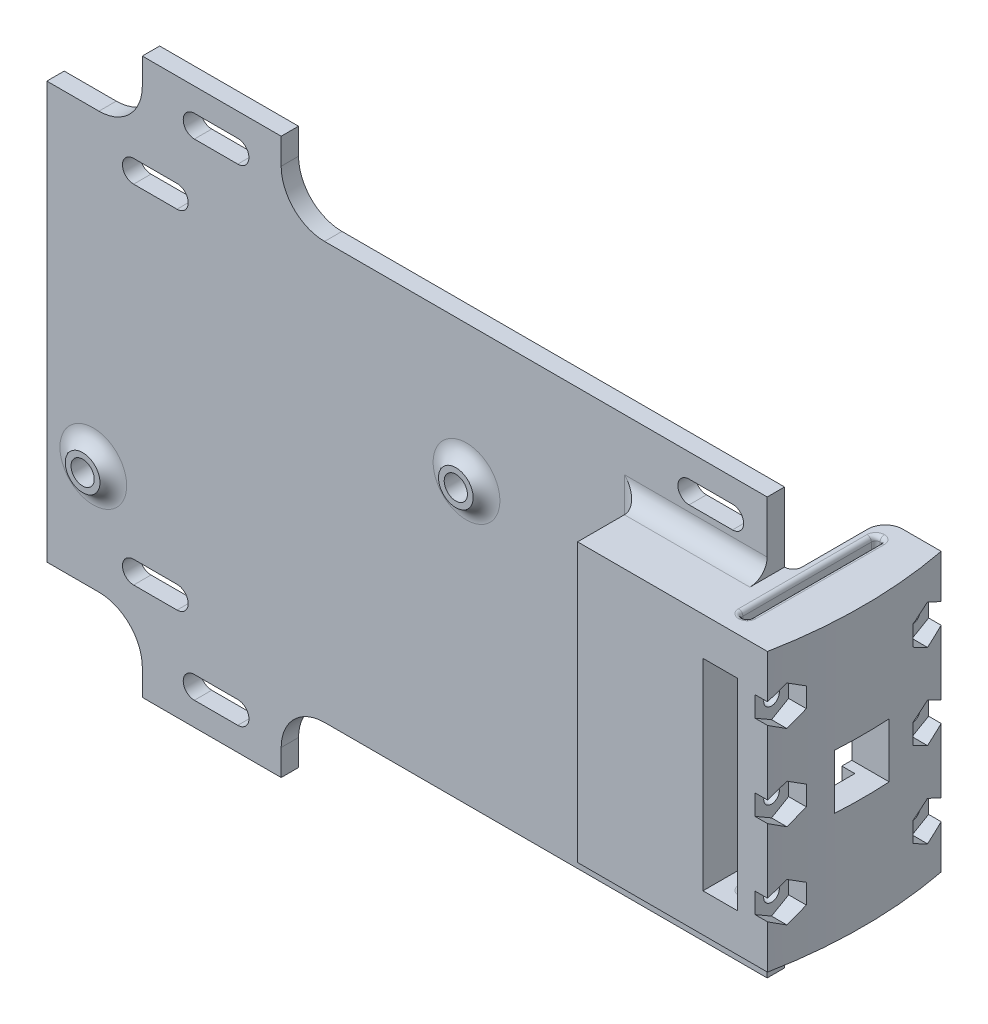
SolidWorks part; units mm, degrees
ref_plane "Front Plane" through (0, 0, 0) normal (0, 0, 1) x (1, 0, 0)
ref_plane "Top Plane" through (0, 0, 0) normal (0, 1, 0) x (1, 0, 0)
ref_plane "Right Plane" through (0, 0, 0) normal (1, 0, 0) x (0, 0, -1)
sketch "Sketch1" plane through (0, 0, 0) normal (0, 0, 1) x (1, 0, 0)
  line L1 (52.705, 30.48) -> (-52.705, 30.48)
  line L2 (52.705, 30.48) -> (52.705, -30.48)
  line L3 (52.705, -30.48) -> (-52.705, -30.48)
  line L4 (-52.705, 30.48) -> (-52.705, -30.48)
  line L5 (52.705, 30.48) -> (-52.705, -30.48) construction
  line L6 (52.705, -30.48) -> (-52.705, 30.48) construction
  point P0 (0, 0)
  dimension "D1" = 105.41
  dimension "D2" = 60.96
extrude "Boss-Extrude1" add sketch "Sketch1" along normal blind 2.54
sketch "Sketch20" plane through (0, 30.48, 0) normal (0, 1, 0) x (1, 0, 0)
  line L0 (52.705, -2.54) -> (-52.705, -2.54) construction
  line L1 (-38.735, -2.54) -> (-18.415, -2.54)
  line L2 (-38.735, -2.54) -> (-38.735, 0)
  line L3 (-38.735, 0) -> (-18.415, 0)
  line L4 (-18.415, -2.54) -> (-18.415, 0)
  line L5 (52.705, 0) -> (-52.705, 0) construction
  line L6 (-52.705, -2.54) -> (-52.705, 0) construction
  dimension "D1" = 13.97
  dimension "D2" = 20.32
extrude "Boss-Extrude5" add sketch "Sketch20" along normal blind 10.16
sketch "Sketch21" plane through (0, -30.48, 0) normal (0, -1, 0) x (-1, 0, 0)
  line L0 (52.705, -2.54) -> (-52.705, -2.54) construction
  line L1 (18.415, -2.54) -> (38.735, -2.54)
  line L2 (18.415, -2.54) -> (18.415, 0)
  line L3 (18.415, 0) -> (38.735, 0)
  line L4 (38.735, -2.54) -> (38.735, 0)
  line L5 (52.705, 0) -> (-52.705, 0) construction
  line L6 (52.705, -2.54) -> (52.705, 0) construction
  dimension "D1" = 13.97
  dimension "D2" = 20.32
extrude "Boss-Extrude6" add sketch "Sketch21" along normal blind 10.16
sketch "Sketch3" plane through (0, 0, 2.54) normal (0, 0, 1) x (1, 0, 0)
  line L0 (0, 0) -> (119.7861, 0) construction
  line L1 (34.356, 20.32) -> (52.705, 20.32)
  line L2 (34.356, 20.32) -> (34.356, -20.32)
  line L3 (34.356, -20.32) -> (52.705, -20.32)
  line L4 (52.705, 20.32) -> (52.705, -20.32)
  line L5 (52.705, -30.48) -> (52.705, 30.48) construction
  dimension "D1" = 40.64
  dimension "D3" = 18.349
extrude "Boss-Extrude2" add sketch "Sketch3" along normal blind 9.398
sketch "Sketch4" plane through (34.356, 0, 0) normal (-1, 0, 0) x (0, 0, 1)
  line L0 (2.54, 20.32) -> (2.54, -20.32) construction
  line L1 (11.0109, 11.43) -> (8.89, 11.43)
  line L2 (11.0109, 11.43) -> (11.0109, -12.5705)
  line L3 (11.0109, -12.5705) -> (8.89, -12.5705)
  line L4 (8.89, 11.43) -> (8.89, -12.5705)
  line L5 (11.938, 20.32) -> (2.54, 20.32) construction
  dimension "D1" = 2.1209
  dimension "D2" = 24.0005
  dimension "D3" = 6.35
  dimension "D4" = 8.89
extrude "SD card Slot" cut sketch "Sketch4" against normal blind 16.51
sketch "Sketch6" plane through (0, 0, 2.54) normal (0, 0, 1) x (1, 0, 0)
  line L0 (50.866, 11.43) -> (50.866, -12.5705) construction
  line L1 (50.866, 11.43) -> (34.356, 11.43) construction
  circle A0 centre (-45.908, -14.954) radius 2.54
  circle A1 centre (8.702, 10.446) radius 2.54
  dimension "D1" = 5.08
  dimension "D2" = 5.08
  dimension "D3" = 54.61
  dimension "D4" = 25.4
  dimension "D5" = 42.164
  dimension "D6" = 0.984
sketch "Sketch5" plane through (0, 0, 0) normal (0, 0, -1) x (-1, 0, 0)
  line L0 (52.705, -30.48) -> (38.735, -30.48) construction
  line L1 (24.765, 35.56) -> (31.115, 35.56) construction
  line L2 (24.765, 37.1919) -> (31.115, 37.1919)
  line L3 (-52.705, -30.48) -> (-52.705, -20.32) construction
  line L4 (-47.625, -25.4) -> (-41.275, -25.4) construction
  line L5 (-47.625, -23.7681) -> (-41.275, -23.7681)
  line L6 (-47.625, -27.032) -> (-41.275, -27.032)
  line L7 (33.655, -25.4) -> (40.005, -25.4) construction
  line L8 (33.655, -23.7681) -> (40.005, -23.7681)
  line L9 (33.655, -27.032) -> (40.005, -27.032)
  line L10 (33.655, 25.4) -> (40.005, 25.4) construction
  line L11 (33.655, 27.0319) -> (40.005, 27.0319)
  line L12 (33.655, 23.768) -> (40.005, 23.768)
  line L13 (-47.625, 25.4) -> (-41.275, 25.4) construction
  line L14 (-47.625, 27.0319) -> (-41.275, 27.0319)
  line L15 (-47.625, 23.768) -> (-41.275, 23.768)
  line L16 (24.765, 33.928) -> (31.115, 33.928)
  line L17 (-11.4366, 0) -> (63.2813, 0) construction
  line L18 (24.765, -35.56) -> (31.115, -35.56) construction
  line L19 (24.765, -37.1919) -> (31.115, -37.1919)
  line L20 (24.765, -33.928) -> (31.115, -33.928)
  arc A0 (33.655, -23.7681) -> (33.655, -27.032) centre (33.655, -25.4) ccw
  arc A1 (40.005, -27.032) -> (40.005, -23.7681) centre (40.005, -25.4) ccw
  arc A2 (33.655, 27.0319) -> (33.655, 23.768) centre (33.655, 25.4) ccw
  arc A3 (40.005, 23.768) -> (40.005, 27.0319) centre (40.005, 25.4) ccw
  arc A4 (-47.625, -23.7681) -> (-47.625, -27.032) centre (-47.625, -25.4) ccw
  arc A5 (-41.275, -27.032) -> (-41.275, -23.7681) centre (-41.275, -25.4) ccw
  arc A6 (-47.625, 27.0319) -> (-47.625, 23.768) centre (-47.625, 25.4) ccw
  arc A7 (-41.275, 23.768) -> (-41.275, 27.0319) centre (-41.275, 25.4) ccw
  arc A8 (24.765, 37.1919) -> (24.765, 33.928) centre (24.765, 35.56) ccw
  arc A9 (31.115, 33.928) -> (31.115, 37.1919) centre (31.115, 35.56) ccw
  arc A10 (24.765, -37.1919) -> (24.765, -33.928) centre (24.765, -35.56) cw
  arc A11 (31.115, -33.928) -> (31.115, -37.1919) centre (31.115, -35.56) cw
  point P3 (27.94, 35.56)
  point P5 (36.83, -25.4)
  point P12 (-44.45, -25.4)
  point P21 (36.83, 25.4)
  point P28 (-44.45, 25.4)
  point P44 (27.94, -35.56)
  dimension "D1" = 1.632
  dimension "D6" = 2
  dimension "D8" = 1.6319
  dimension "D4" = 5.08
  dimension "D5" = 5.08
  dimension "D2" = 6.35
  dimension "D7" = 10.16
  dimension "D9" = 2.54
  dimension "D10" = 6.35
  dimension "D3" = 2
extrude "Mounting slots" cut sketch "Sketch5" against normal up to next
sketch "Sketch8" plane through (52.705, 0, 0) normal (1, 0, 0) x (0, 0, -1)
  line L1 (-11.938, -20.32) -> (13.462, -20.32)
  line L2 (-11.938, -20.32) -> (-11.938, 20.32)
  line L3 (-11.938, 20.32) -> (13.462, 20.32)
  line L4 (13.462, -20.32) -> (13.462, 20.32)
  line L6 (-9.1929, 0) -> (7.5537, 0) construction
  line L7 (0.762, 4.5369) -> (0.762, -4.1382) construction
  line L8 (0, -30.48) -> (0, 30.48) construction
  line L9 (-11.938, 20.32) -> (-2.54, 20.32) construction
  line L11 (-11.938, -20.32) -> (-2.54, -20.32) construction
  dimension "D1" = 25.4
  dimension "D2" = 0.762
extrude "Camera Mount" add sketch "Sketch8" along normal blind 38.1
sketch "Sketch9" plane through (0, 0, 2.54) normal (0, 0, 1) x (1, 0, 0)
  line L0 (-53.0586, 25.8373) -> (58.7014, -24.9627) construction
  line L1 (58.7014, 25.8373) -> (-53.0586, -24.9627) construction
  line L2 (58.7014, 25.8373) -> (-53.0586, 25.8373) construction
  line L3 (58.7014, 25.8373) -> (58.7014, -24.9627) construction
  line L4 (58.7014, -24.9627) -> (-53.0586, -24.9627) construction
  line L5 (-53.0586, 25.8373) -> (-53.0586, -24.9627) construction
  line L6 (0, 0) -> (-38.1087, 0) construction
  line L7 (-63.8536, -101.1627) -> (69.4964, -101.1627)
  line L8 (-63.8536, -101.1627) -> (-63.8536, 102.0373)
  line L9 (-63.8536, 102.0373) -> (69.4964, 102.0373)
  line L10 (69.4964, -101.1627) -> (69.4964, 102.0373)
  line L11 (-63.8536, -101.1627) -> (69.4964, 102.0373) construction
  line L12 (-63.8536, 102.0373) -> (69.4964, -101.1627) construction
  line L13 (52.705, 14.732) -> (57.785, 14.732)
  line L14 (52.705, 14.732) -> (52.705, -14.732)
  line L15 (52.705, -14.732) -> (57.785, -14.732)
  line L16 (57.785, 14.732) -> (57.785, -14.732)
  line L17 (52.705, 20.32) -> (52.705, 30.48) construction
  arc A6 (-40.005, 27.0319) -> (-40.005, 23.768) centre (-40.005, 25.4) ccw construction
  point P0 (2.8214, 0.4373)
  point P10 (-41.6369, 25.4)
  dimension "D1" = 111.76
  dimension "D2" = 50.8
  dimension "D3" = 133.35
  dimension "D4" = 203.2
  dimension "D5" = 5.08
  dimension "D6" = 29.464
  dimension "D7" = 11.43
sketch "Sketch10" plane through (0, 30.48, 0) normal (0, 1, 0) x (1, 0, 0)
  line L1 (52.705, 0) -> (-18.415, 0) construction
  line L2 (0, -1.8666) -> (0, 5.5247) construction
  line L4 (-124.1786, 120.847) -> (129.8214, 120.847)
  line L5 (-124.1786, 120.847) -> (-124.1786, -133.153)
  line L6 (-124.1786, -133.153) -> (129.8214, -133.153)
  line L7 (129.8214, 120.847) -> (129.8214, -133.153)
  circle A0 centre (-3.302, 0.8001) radius 66.675
  dimension "D2" = 133.35
  dimension "D1" = 0.8001
  dimension "D3" = 254
  dimension "D4" = 254
  dimension "D5" = 3.302
extrude "Cut-Extrude7" cut sketch "Sketch10" against normal through all and the other way through all
extrude "Cut-Extrude8" cut sketch "Sketch9" against normal through all and the other way through all from offset 4.064 contours L16 L15 L14 L13 offset against normal yes
sketch "Sketch11" plane through (57.785, 0, 0) normal (-1, 0, 0) x (0, 0, 1)
  line L0 (-0.762, -33.2662) -> (-0.762, 42.8989) construction
  line L2 (23.6947, 0) -> (-23.921, 0) construction
  line L4 (0, -30.48) -> (0, -20.32) construction
  line L5 (3.2385, 4.0005) -> (-4.7625, 4.0005)
  line L6 (3.2385, 4.0005) -> (3.2385, -4.0005)
  line L7 (3.2385, -4.0005) -> (-4.7625, -4.0005)
  line L8 (-4.7625, 4.0005) -> (-4.7625, -4.0005)
  line L9 (3.2385, 4.0005) -> (-4.7625, -4.0005) construction
  line L10 (3.2385, -4.0005) -> (-4.7625, 4.0005) construction
  line L12 (-13.462, -14.732) -> (11.938, -14.732) construction
  line L13 (-13.462, 14.732) -> (11.938, 14.732) construction
  circle A0 centre (9.525, 0) radius 1.143
  circle A1 centre (-11.049, 0) radius 1.143
  circle A2 centre (-11.049, 12.446) radius 1.143
  circle A3 centre (9.525, 12.446) radius 1.143
  circle A4 centre (-11.049, -12.446) radius 1.143
  circle A5 centre (9.525, -12.446) radius 1.143
  point P8 (-0.762, 0)
  dimension "D5" = 2.286
  dimension "D6" = 2.286
  dimension "D1" = 0.762
  dimension "D3" = 8.001
  dimension "D4" = 8.001
  dimension "D7" = 20.574
  dimension "D8" = 2
  dimension "D9" = 2
extrude "Camera holes" cut sketch "Sketch11" against normal through all
sketch "Sketch15" plane through (57.785, 0, 0) normal (-1, 0, 0) x (0, 0, 1)
  line L0 (7.025, 11.0026) -> (9.525, 9.5593)
  line L1 (-8.549, 11.0026) -> (-8.549, 13.8894)
  line L2 (-8.549, 13.8894) -> (-11.049, 15.3327)
  line L3 (-11.049, 15.3327) -> (-13.549, 13.8894)
  line L4 (-13.549, 13.8894) -> (-13.549, 11.0026)
  line L5 (-13.549, 11.0026) -> (-11.049, 9.5593)
  line L6 (-11.049, 9.5593) -> (-8.549, 11.0026)
  line L7 (9.525, 9.5593) -> (12.025, 11.0026)
  line L8 (12.025, 11.0026) -> (12.025, 13.8894)
  line L9 (12.025, 13.8894) -> (9.525, 15.3327)
  line L10 (9.525, 15.3327) -> (7.025, 13.8894)
  line L11 (7.025, 13.8894) -> (7.025, 11.0026)
  line L12 (7.025, -1.4434) -> (9.525, -2.8867)
  line L13 (9.525, -2.8867) -> (12.025, -1.4434)
  line L14 (12.025, -1.4434) -> (12.025, 1.4434)
  line L15 (12.025, 1.4434) -> (9.525, 2.8867)
  line L16 (9.525, 2.8867) -> (7.025, 1.4434)
  line L17 (7.025, 1.4434) -> (7.025, -1.4434)
  line L18 (7.025, -13.8894) -> (9.525, -15.3327)
  line L19 (9.525, -15.3327) -> (12.025, -13.8894)
  line L20 (12.025, -13.8894) -> (12.025, -11.0026)
  line L21 (12.025, -11.0026) -> (9.525, -9.5593)
  line L22 (9.525, -9.5593) -> (7.025, -11.0026)
  line L23 (7.025, -11.0026) -> (7.025, -13.8894)
  line L24 (-13.549, -1.4434) -> (-11.049, -2.8867)
  line L25 (-11.049, -2.8867) -> (-8.549, -1.4434)
  line L26 (-8.549, -1.4434) -> (-8.549, 1.4434)
  line L27 (-8.549, 1.4434) -> (-11.049, 2.8867)
  line L28 (-11.049, 2.8867) -> (-13.549, 1.4434)
  line L29 (-13.549, 1.4434) -> (-13.549, -1.4434)
  line L30 (-13.549, -13.8894) -> (-11.049, -15.3327)
  line L31 (-11.049, -15.3327) -> (-8.549, -13.8894)
  line L32 (-8.549, -13.8894) -> (-8.549, -11.0026)
  line L33 (-8.549, -11.0026) -> (-11.049, -9.5593)
  line L34 (-11.049, -9.5593) -> (-13.549, -11.0026)
  line L35 (-13.549, -11.0026) -> (-13.549, -13.8894)
  circle A3 centre (-11.049, 12.446) radius 2.5 construction
  dimension "D1" = 2
  dimension "D2" = 3
  dimension "D4" = 5
extrude "M2.5 camera nut" cut sketch "Sketch15" against normal up to next from offset 2.54 offset against normal yes
extrude "Boss-Extrude4" add sketch "Sketch6" along normal blind 1.5621
sketch "Sketch18" plane through (0, 0, 4.1021) normal (0, 0, 1) x (1, 0, 0)
  circle A0 centre (8.702, 10.446) radius 1.4605
  circle A1 centre (-45.908, -14.954) radius 1.4605
  dimension "D1" = 2.921
  dimension "D2" = 2.921
extrude "Cut-Extrude13" cut sketch "Sketch18" against normal through all
sketch "Sketch29" plane through (0, 0, 0) normal (0, 0, -1) x (-1, 0, 0)
  line L1 (47.4957, -17.704) -> (49.0834, -14.954)
  line L2 (49.0834, -14.954) -> (47.4957, -12.204)
  line L3 (47.4957, -12.204) -> (44.3202, -12.204)
  line L4 (44.3202, -12.204) -> (42.7325, -14.954)
  line L5 (42.7325, -14.954) -> (44.3202, -17.704)
  line L6 (44.3202, -17.704) -> (47.4957, -17.704)
  line L7 (-5.5266, 10.446) -> (-7.1143, 13.196)
  line L8 (-7.1143, 13.196) -> (-10.2898, 13.196)
  line L9 (-10.2898, 13.196) -> (-11.8775, 10.446)
  line L10 (-11.8775, 10.446) -> (-10.2898, 7.696)
  line L11 (-10.2898, 7.696) -> (-7.1143, 7.696)
  line L12 (-7.1143, 7.696) -> (-5.5266, 10.446)
  circle A0 centre (45.908, -14.954) radius 2.75 construction
  circle A1 centre (-8.702, 10.446) radius 2.75 construction
  dimension "D1" = 5.5
  dimension "D2" = 5.5
extrude "hex holes" cut sketch "Sketch29" against normal blind 1.27
hole_wizard "M3 Clearance Hole1" positions "Sketch31" profile "Sketch30" hole size "M3" standard "ANSI Metric"
sketch "Sketch31" plane through (0, 0, 0) normal (0, 0, -1) x (-1, 0, 0)
  point P0 (45.908, -14.954)
  point P3 (-8.702, 10.446)
sketch "Sketch30" plane through (-45.908, -14.954, 0) normal (1, 0, 0) x (0, 1, 0)
  line L0 (0, 0) -> (0, 11.0214)
  line L1 (0, 11.0214) -> (1.7, 10)
  line L2 (1.7, 10) -> (1.7, 0)
  line L5 (1.7, 0) -> (0, 0)
  line L10 (0, 11.0214) -> (-1.7, 10) construction
  line L11 (0, -6.35) -> (0, 107.95) construction
  dimension "Hole Dia." = 3.4
  dimension "Hole Depth" = 10
  dimension "Drill Angle" = 118
sketch "Sketch32" plane through (57.785, 0, 0) normal (-1, 0, 0) x (0, 0, 1)
  line L0 (-0.762, -4.0005) -> (-0.762, 4.0005) construction
  line L1 (-4.7625, -4.0005) -> (3.2385, -4.0005) construction
  line L2 (3.2385, 4.0005) -> (-4.7625, 4.0005) construction
  line L3 (-13.462, 14.732) -> (11.938, 14.732) construction
  line L4 (1.778, -14.732) -> (-3.302, -14.732)
  line L5 (1.778, -14.732) -> (1.778, 14.732)
  line L6 (1.778, 14.732) -> (-3.302, 14.732)
  line L7 (-3.302, -14.732) -> (-3.302, 14.732)
  line L8 (1.778, -14.732) -> (-3.302, 14.732) construction
  line L9 (1.778, 14.732) -> (-3.302, -14.732) construction
  point P6 (-0.762, 0)
  dimension "D1" = 5.08
extrude "Cut-Extrude14" cut sketch "Sketch32" against normal blind 1.905
sketch "Sketch33" plane through (0, 20.32, 0) normal (0, 1, 0) x (1, 0, 0)
  line L0 (57.785, -1.778) -> (57.785, -11.938) construction
  line L4 (55.245, 10.795) -> (56.515, 10.795)
  line L5 (55.245, 10.795) -> (55.245, -9.271)
  line L6 (55.245, -9.271) -> (56.515, -9.271)
  line L7 (56.515, 10.795) -> (56.515, -9.271)
  line L8 (55.245, 10.795) -> (56.515, -9.271) construction
  line L9 (55.245, -9.271) -> (56.515, 10.795) construction
  line L10 (67.243, 0.762) -> (56.7168, 0.762) construction
  line L11 (62.1449, -11.938) -> (34.356, -11.938) construction
  line L12 (62.1597, 13.462) -> (52.705, 13.462) construction
  point P7 (55.88, 0.762)
  dimension "D1" = 1.27
  dimension "D2" = 20.066
  dimension "D3" = 1.27
extrude "Cut-Extrude15" cut sketch "Sketch33" against normal through all
sketch "Sketch34" plane through (0, 20.32, 0) normal (0, 1, 0) x (1, 0, 0)
  line L1 (52.705, 0) -> (53.975, 0)
  line L2 (52.705, 0) -> (52.705, 28.5232)
  line L3 (52.705, 28.5232) -> (53.975, 28.5232)
  line L4 (53.975, 0) -> (53.975, 28.5232)
  dimension "D1" = 1.27
extrude "Cut-Extrude16" cut sketch "Sketch34" against normal through all
fillet "Fillet4" radius 0.635 16 edges at (55.245, 20.32, -0.762) (55.245, 14.732, -0.762) (55.245, -20.32, -0.762) (56.515, -20.32, -0.762) (56.515, -14.732, -0.762) (55.245, -14.732, -0.762) (56.515, 17.526, -10.795) (56.515, 20.32, -0.762) (56.515, 17.526, 9.271) (56.515, 14.732, -0.762) (56.515, -17.526, 9.271) (55.245, -17.526, 9.271) (55.245, -17.526, -10.795) (56.515, -17.526, -10.795) (55.245, 17.526, -10.795) (55.245, 17.526, 9.271)
fillet "Fillet1" radius 2.54 2 edges at (-48.448, -14.954, 2.54) (6.162, 10.446, 2.54)
fillet "Fillet2" radius 2.54 3 edges at (34.356, 0, 2.54)
fillet "Fillet3" radius 6.35 4 edges
fillet "Fillet5" radius 1.27 2 edges at (53.975, -17.526, 0) (53.975, 17.526, 0)
fillet "Fillet6" radius 2.54 2 edges at (53.975, -17.526, -13.462) (53.975, 17.526, -13.462)
